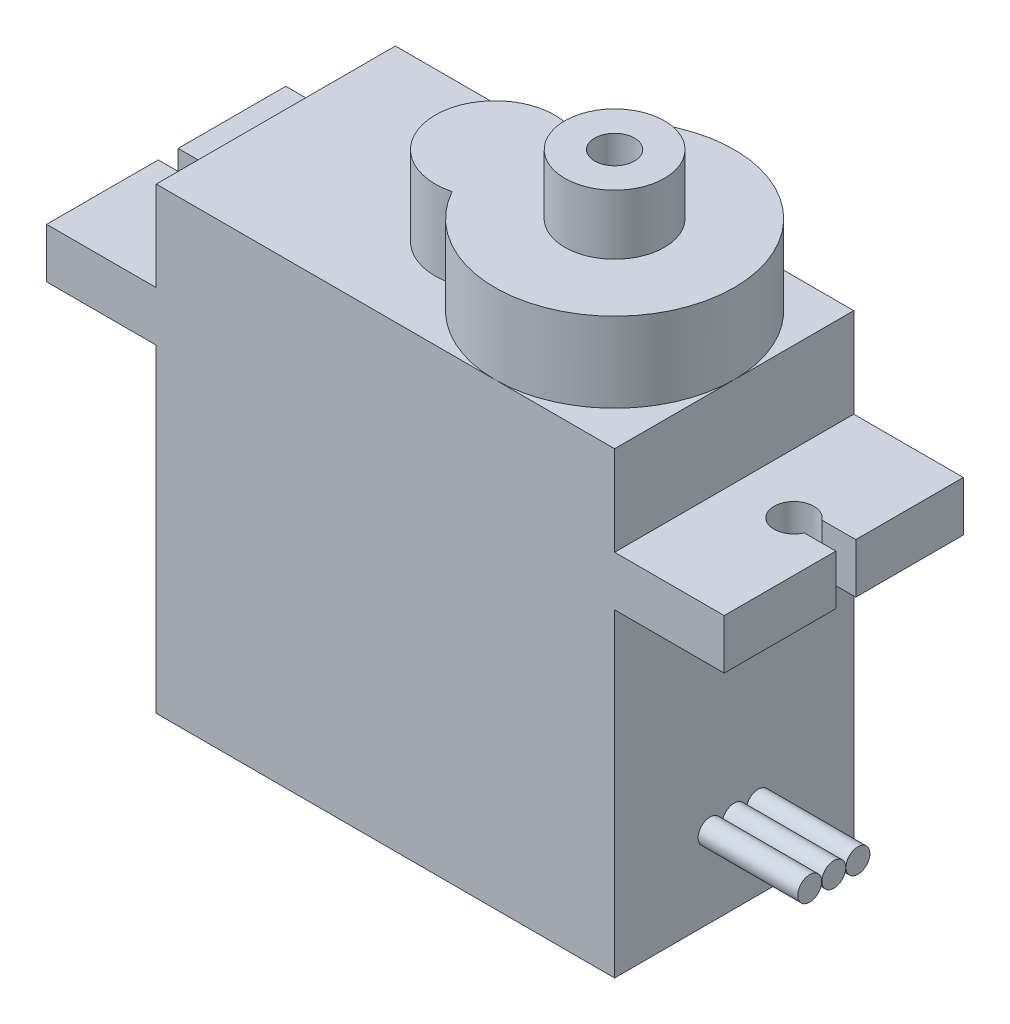
SolidWorks part; units mm, degrees
ref_plane "Front Plane" through (0, 0, 0) normal (0, 0, 1) x (1, 0, 0)
ref_plane "Top Plane" through (0, 0, 0) normal (0, 1, 0) x (1, 0, 0)
ref_plane "Right Plane" through (0, 0, 0) normal (1, 0, 0) x (0, 0, -1)
sketch "Sketch1" plane through (0, 0, 0) normal (0, 1, 0) x (1, 0, 0)
  line L1 (-11.5, -6) -> (11.5, -6)
  line L2 (-11.5, -6) -> (-11.5, 6)
  line L3 (-11.5, 6) -> (11.5, 6)
  line L4 (11.5, -6) -> (11.5, 6)
  line L5 (-11.5, -6) -> (11.5, 6) construction
  line L6 (-11.5, 6) -> (11.5, -6) construction
  point P0 (0, 0)
  dimension "D1" = 12
  dimension "D2" = 23
extrude "Boss-Extrude1" add sketch "Sketch1" along normal blind 23
sketch "Sketch2" plane through (-11.5, 0, 0) normal (-1, 0, 0) x (0, 0, 1)
  line L0 (-6, 23) -> (-6, 0) construction
  line L1 (-6, 18.5) -> (6, 18.5)
  line L2 (-6, 18.5) -> (-6, 16)
  line L3 (-6, 16) -> (6, 16)
  line L4 (6, 18.5) -> (6, 16)
  line L5 (6, 23) -> (6, 0) construction
  line L6 (-6, 0) -> (6, 0) construction
  dimension "D1" = 16
  dimension "D2" = 2.5
extrude "Boss-Extrude2" add sketch "Sketch2" along normal blind 5.5
sketch "Sketch3" plane through (0, 18.5, 0) normal (0, 1, 0) x (1, 0, 0)
  line L0 (-17, -6) -> (-17, 6) construction
  line L1 (-17, 0.6) -> (-15.3, 0.6)
  line L2 (-17, 0.6) -> (-17, -0.4)
  line L4 (-17, -0.4) -> (-15.4165, -0.4)
  line L6 (-11.5, -6) -> (-11.5, 6) construction
  arc A0 (-15.4165, -0.4) -> (-15.3, 0.6) centre (-14.5, 0) ccw
  point P10 (-11.5, 0)
  dimension "D1" = 2.5
  dimension "D2" = 2
  dimension "D3" = 1
extrude "Cut-Extrude1" cut sketch "Sketch3" against normal blind 5
mirror "Mirror1" about plane through (0, 0, 0) normal (1, 0, 0) of "Cut-Extrude1", "Boss-Extrude2"
sketch "Sketch4" plane through (0, 23, 0) normal (0, 1, 0) x (1, 0, 0)
  line L1 (11.5, -6) -> (11.5, 6) construction
  arc A0 (0.25, -2.9047) -> (0.25, 2.9047) centre (5.5, 0) ccw
  arc A1 (0.25, 2.9047) -> (0.25, -2.9047) centre (-0.5, 0) ccw
  dimension "D1" = 12
  dimension "D3" = 6
  dimension "D4" = 6
  dimension "D2" = 6
extrude "Boss-Extrude3" add sketch "Sketch4" along normal blind 4
sketch "Sketch5" plane through (0, 27, 0) normal (0, 1, 0) x (1, 0, 0)
  circle A0 centre (5.5, 0) radius 2.5
  circle A1 centre (5.5, 0) radius 6 construction
  circle A2 centre (5.5, 0) radius 1
  dimension "D1" = 0
  dimension "D2" = 5
  dimension "D3" = 2
extrude "Boss-Extrude4" add sketch "Sketch5" along normal blind 3
sketch "Sketch7" plane through (11.5, 0, 0) normal (1, 0, 0) x (0, 0, -1)
  line L0 (-6, 0) -> (6, 0) construction
  circle A0 centre (0, 4) radius 0.6
  circle A1 centre (1.21, 4) radius 0.6
  circle A2 centre (-1.21, 4) radius 0.6
  dimension "D1" = 1.2
  dimension "D2" = 1.2
  dimension "D3" = 1.2
  dimension "D4" = 4
  dimension "D5" = 1.21
  dimension "D6" = 1.21
extrude "Boss-Extrude8" add sketch "Sketch7" along normal blind 5
